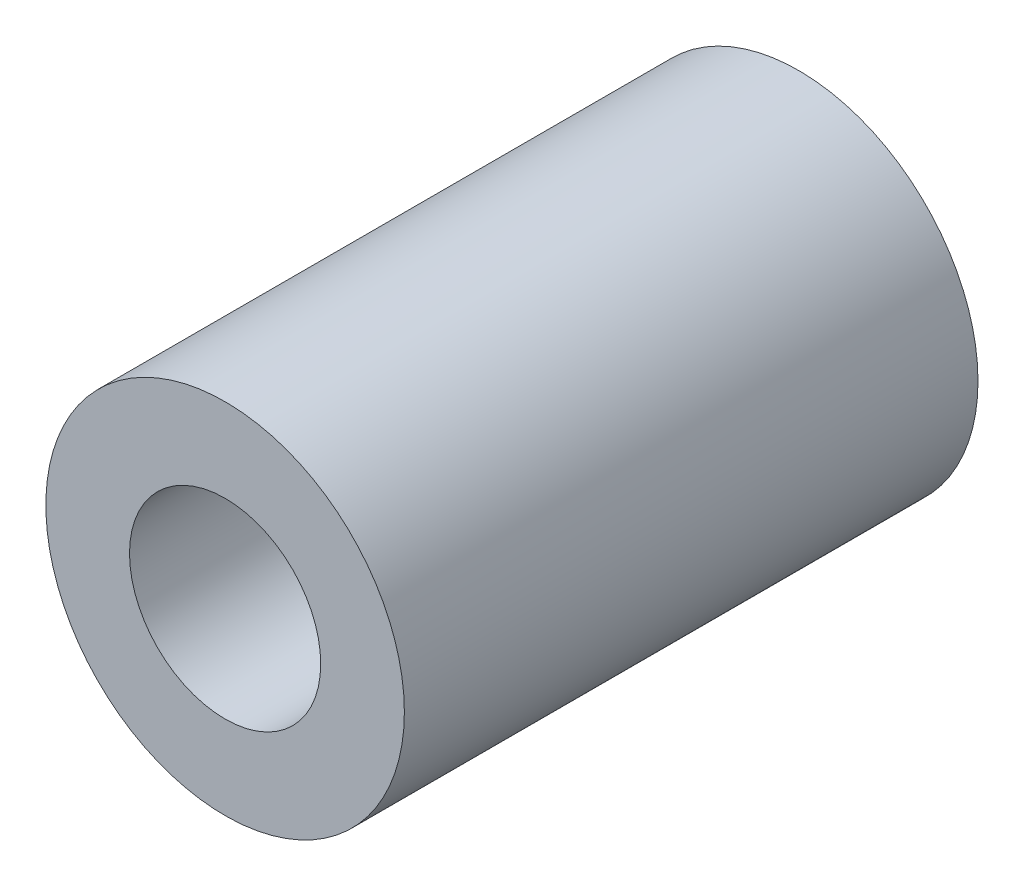
SolidWorks part; units mm, degrees
ref_plane "Plan de face" through (0, 0, 0) normal (0, 0, 1) x (1, 0, 0)
ref_plane "Plan de dessus" through (0, 0, 0) normal (0, 1, 0) x (1, 0, 0)
ref_plane "Plan de droite" through (0, 0, 0) normal (1, 0, 0) x (0, 0, -1)
sketch "Esquisse2" plane through (0, 0, 0) normal (0, 0, 1) x (1, 0, 0)
  circle A0 centre (0, 0) radius 7.5
  circle A1 centre (0, 0) radius 4
extrude "Boss.-Extru.1" add sketch "Esquisse2" along normal blind 12 and the other way blind 12
